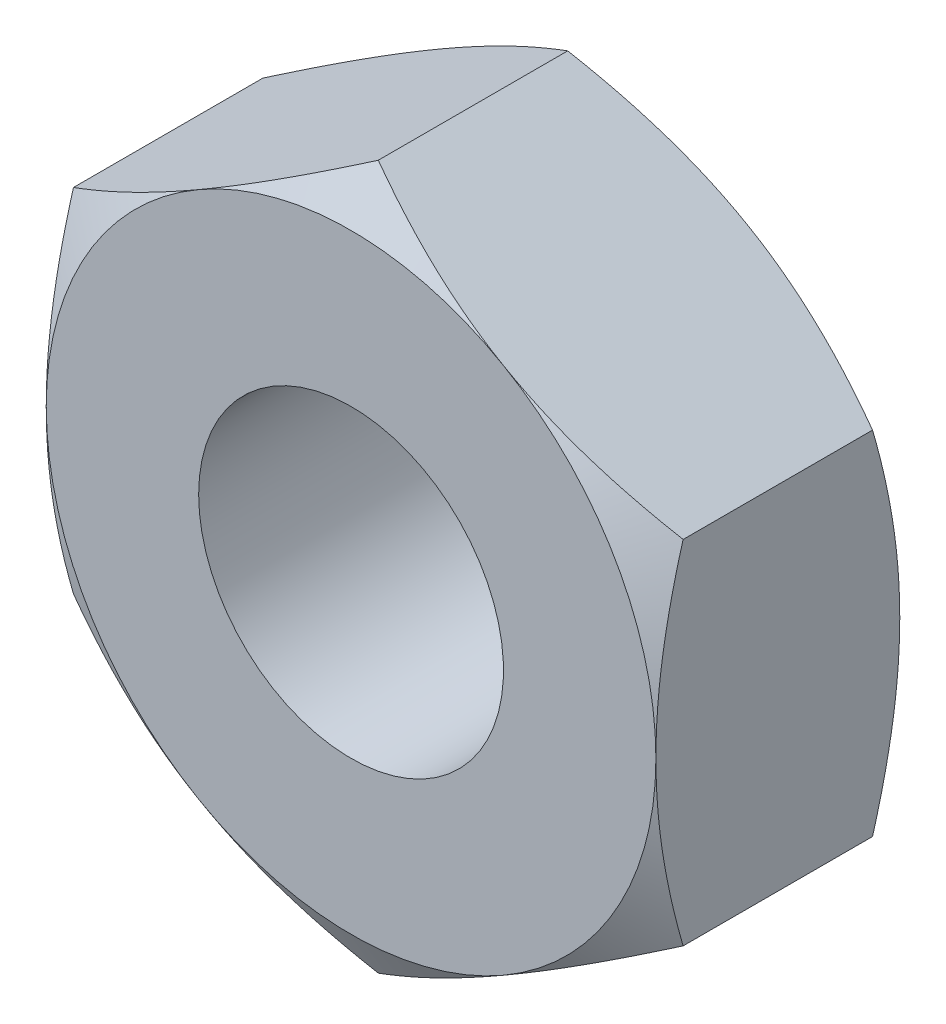
SolidWorks part; units mm, degrees
ref_plane "Front" through (0, 0, 0) normal (0, 0, 1) x (1, 0, 0)
ref_plane "Top" through (0, 0, 0) normal (0, 1, 0) x (1, 0, 0)
ref_plane "Right" through (0, 0, 0) normal (1, 0, 0) x (0, 0, -1)
sketch "Sketch1" plane through (0, 0, 0) normal (0, 0, 1) x (1, 0, 0)
  line L1 (-2, 1.1547) -> (-2, -1.1547)
  line L2 (-2, -1.1547) -> (0, -2.3094)
  line L3 (0, -2.3094) -> (2, -1.1547)
  line L4 (2, -1.1547) -> (2, 1.1547)
  line L5 (2, 1.1547) -> (0, 2.3094)
  line L6 (0, 2.3094) -> (-2, 1.1547)
  circle A0 centre (0, 0) radius 2 construction
  circle A1 centre (0, 0) radius 1 construction
  point P10 (0, 1)
  dimension "hex" = 4
  dimension "dia" = 2
extrude "Extrude1" add sketch "Sketch1" along normal mid plane 1.6
sketch "Sketch4" plane through (0, 0, -0.8) normal (0, 0, -1) x (-1, 0, 0)
  circle A0 centre (0, 0) radius 1 construction
  circle A1 centre (0, 0) radius 1
sketch "Sketch10" plane through (0, 0, 0.8) normal (0, 0, 1) x (1, 0, 0)
  circle A0 centre (0, 0) radius 1 construction
  circle A1 centre (0, 0) radius 1
extrude "Cut-Extrude2" cut sketch "Sketch10" against normal through all draft 45
sketch "Sketch11" plane through (0, 0, -0.8) normal (0, 0, -1) x (-1, 0, 0)
  circle A0 centre (0, 0) radius 1 construction
  circle A1 centre (0, 0) radius 1
extrude "Cut-Extrude3" cut sketch "Sketch11" against normal through all draft 45
sketch "Sketch13" plane through (0, 0, -0.8) normal (0, 0, -1) x (-1, 0, 0)
  circle A0 centre (0, 0) radius 1 construction
  circle A1 centre (0, 0) radius 1
extrude "Boss-Extrude1" add sketch "Sketch13" against normal up to vertex separate body up to point (0, -2, 1.1547)
curve "Helix/Spiral3" [suppressed] pitch 0.4 height 1.6 turns 4
sketch "Sketch12" plane through (0, 0, 0) normal (1, 0, 0) x (0, 0, -1)
  line L0 (1.15, 1) -> (0.8, 1)
  line L1 (1.15, 1) -> (1, 0.7402)
  line L2 (1, 0.7402) -> (0.95, 0.7402)
  line L3 (0.95, 0.7402) -> (0.8, 1)
  line L4 (0.975, 0.7402) -> (0.975, 1) construction
  line L5 (0.875, 0.8701) -> (1.075, 0.8701) construction
  dimension "D1" = 60
  dimension "D2" = 0.05
  dimension "D3" = 0.2
sweep "Cut-Sweep1" [suppressed] cut profiles "Sketch12" path "Helix/Spiral3"
combine bodies "Combine1" operation type subtract main body 116 bodies to subtract 117
sketch "Sketch7" plane through (0, 0, 0.8) normal (0, 0, 1) x (1, 0, 0)
  circle A0 centre (0, 0) radius 2 construction
  circle A1 centre (0, 0) radius 2
extrude "Extrude2" cut sketch "Sketch7" against normal blind 25.4 draft 60 flip side to cut
mirror "Mirror2" about plane through (0, 0, 0) normal (0, 0, 1) of "Extrude2"
sketch "Sketch8" plane through (0, 0, 0.8) normal (0, 0, 1) x (1, 0, 0)
  line L0 (-0.7071, 0.7071) -> (0, 0) construction
  line L1 (0, -1.004) -> (0, 1.004) construction
  circle A1 centre (0, 0) radius 1 construction
  point P0 (-0.7071, 0.7071)
  dimension "D1" = 45
equation "\"D3@Helix/Spiral3\" = \"length@Extrude1\" "
equation "\"D2@Sketch12\" = \"D4@Helix/Spiral3\"*.125"
equation "\"D3@Sketch12\" = \"D4@Helix/Spiral3\"*.50"
